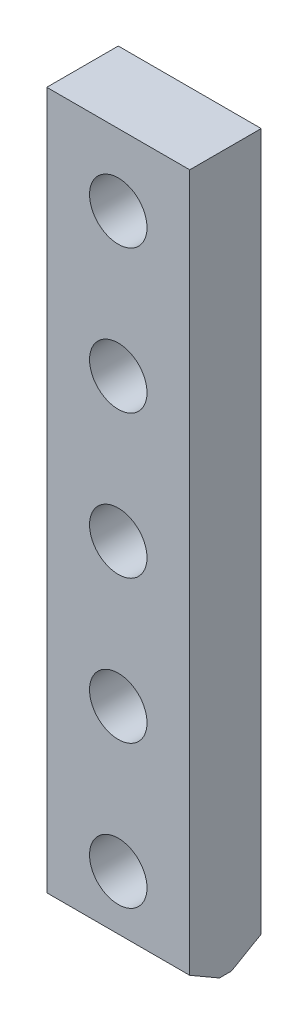
SolidWorks part; units mm, degrees
ref_plane "Спереди" through (0, 0, 0) normal (0, 0, 1) x (1, 0, 0)
ref_plane "Сверху" through (0, 0, 0) normal (0, 1, 0) x (1, 0, 0)
ref_plane "Справа" through (0, 0, 0) normal (1, 0, 0) x (0, 0, -1)
sketch "Эскиз1" plane through (0, 0, 0) normal (0, 0, 1) x (1, 0, 0)
  line L1 (0, 0) -> (50, 0)
  line L2 (0, 0) -> (0, 250)
  line L3 (0, 250) -> (50, 250)
  line L4 (50, 0) -> (50, 250)
  point P5 (25, 250)
  dimension "D1" = 250
  dimension "D2" = 50
extrude "Бобышка-Вытянуть1" add sketch "Эскиз1" along normal blind 25
sketch "Эскиз2" plane through (0, 0, 25) normal (0, 0, 1) x (1, 0, 0)
  line L0 (0, 0) -> (50, 0) construction
  line L1 (50, 0) -> (50, 250) construction
  circle A0 centre (25, 25) radius 10.05
  circle A1 centre (25, 75) radius 10.05
  circle A2 centre (25, 125) radius 10.05
  circle A3 centre (25, 175) radius 10.05
  circle A4 centre (25, 225) radius 10.05
  dimension "D1" = 5
  dimension "D2" = 25
  dimension "D3" = 25
  dimension "D4" = 20.1
extrude "Вырез-Вытянуть1" cut sketch "Эскиз2" against normal through all
chamfer "Фаска1" distance 6 angle 60 1 edges at (25, 0, 0) first distance on face at (35.05, 75, 0)
chamfer "Фаска2" distance 6 angle 60 1 edges at (25, 0, 25) first distance on face at (35.05, 75, 25)
